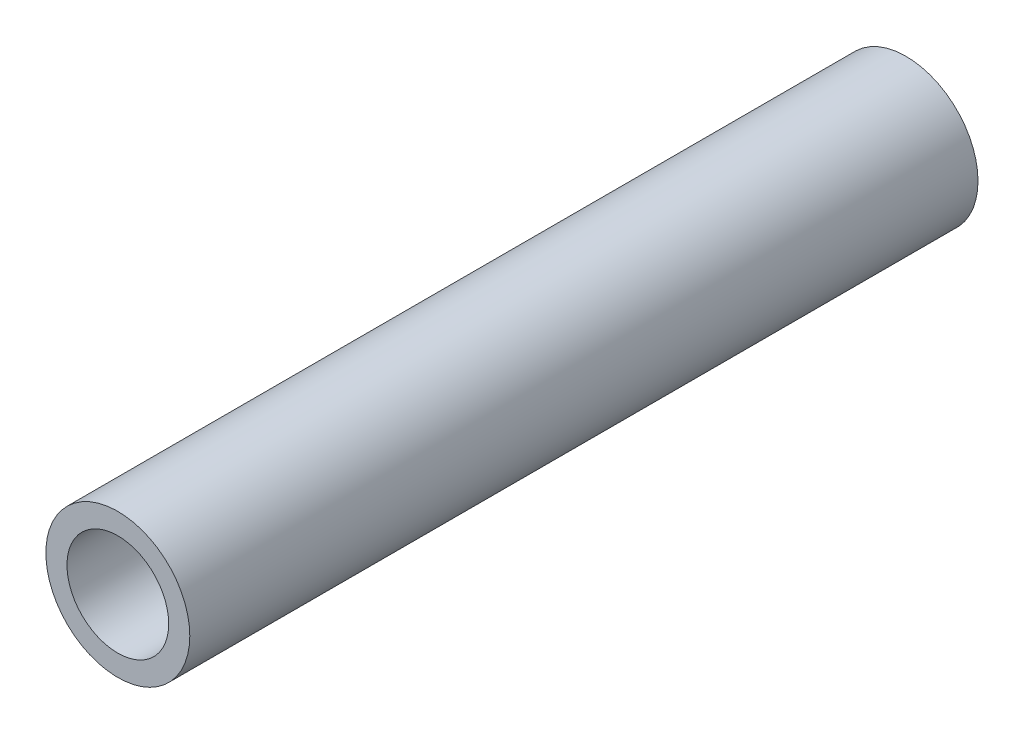
SolidWorks part; units mm, degrees
ref_plane "Front Plane" through (0, 0, 0) normal (0, 0, 1) x (1, 0, 0)
ref_plane "Top Plane" through (0, 0, 0) normal (0, 1, 0) x (1, 0, 0)
ref_plane "Right Plane" through (0, 0, 0) normal (1, 0, 0) x (0, 0, -1)
sketch "Sketch1" plane through (0, 0, 0) normal (0, 0, 1) x (1, 0, 0)
  circle A0 centre (0, 0) radius 13.335
  dimension "Pipe OD" = 26.67
extrude "Extrude-Thin1" add sketch "Sketch1" along normal mid plane 146.05 thin thin type one direction reverse wall 3.9116
